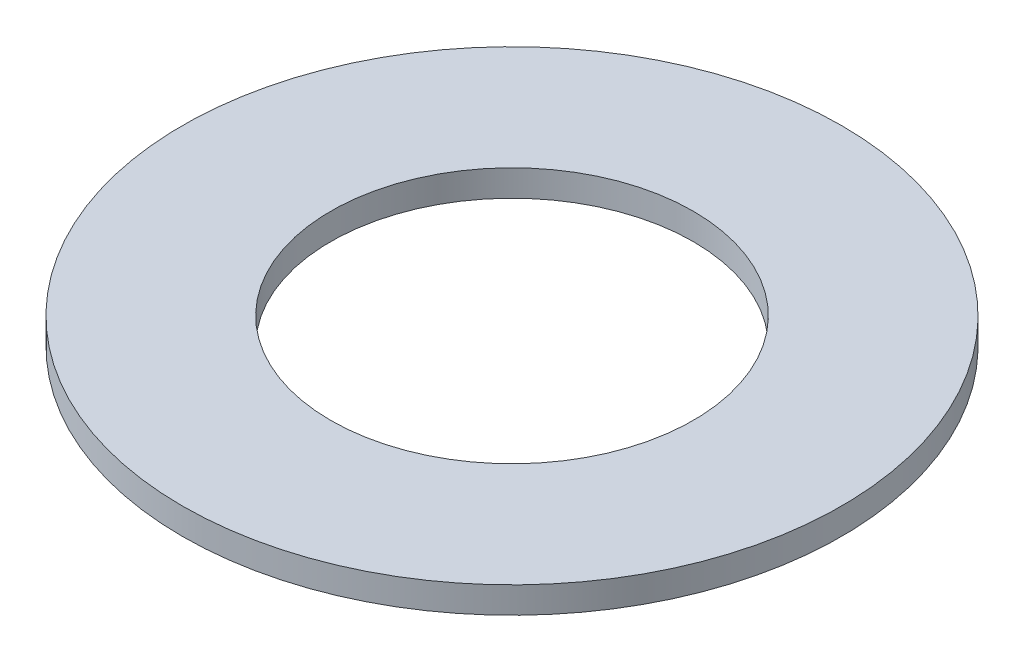
SolidWorks part; units mm, degrees
ref_plane "Front Plane" through (0, 0, 0) normal (0, 0, 1) x (1, 0, 0)
ref_plane "Top Plane" through (0, 0, 0) normal (0, 1, 0) x (1, 0, 0)
ref_plane "Right Plane" through (0, 0, 0) normal (1, 0, 0) x (0, 0, -1)
sketch "Sketch1" plane through (0, 0, 0) normal (0, 1, 0) x (1, 0, 0)
  circle A0 centre (0, 0) radius 50
  dimension "FLANGE_OD" = 100
extrude "Boss-Extrude1" add sketch "Sketch1" along normal blind 4
sketch "Sketch2" plane through (0, 0, 0) normal (0, 1, 0) x (1, 0, 0)
  circle A0 centre (0, 0) radius 27.5
  dimension "BORE_D" = 55
extrude "Cut-Extrude1" cut sketch "Sketch2" along normal through all
sketch "Sketch3" plane through (0, 4, 0) normal (0, 1, 0) x (1, 0, 0)
  circle A0 centre (0, 0) radius 19.5137 construction
  circle A1 centre (-19.5137, 0) radius 2.361
  dimension "BOLT_D" = 4.722
  dimension "BOLT_PCD" = 39.0273
extrude "Cut-Extrude2" cut sketch "Sketch3" against normal blind 3.1855 rebuild error yes
pattern_circular "CirPattern1" count 6 over 360 rebuild error yes
